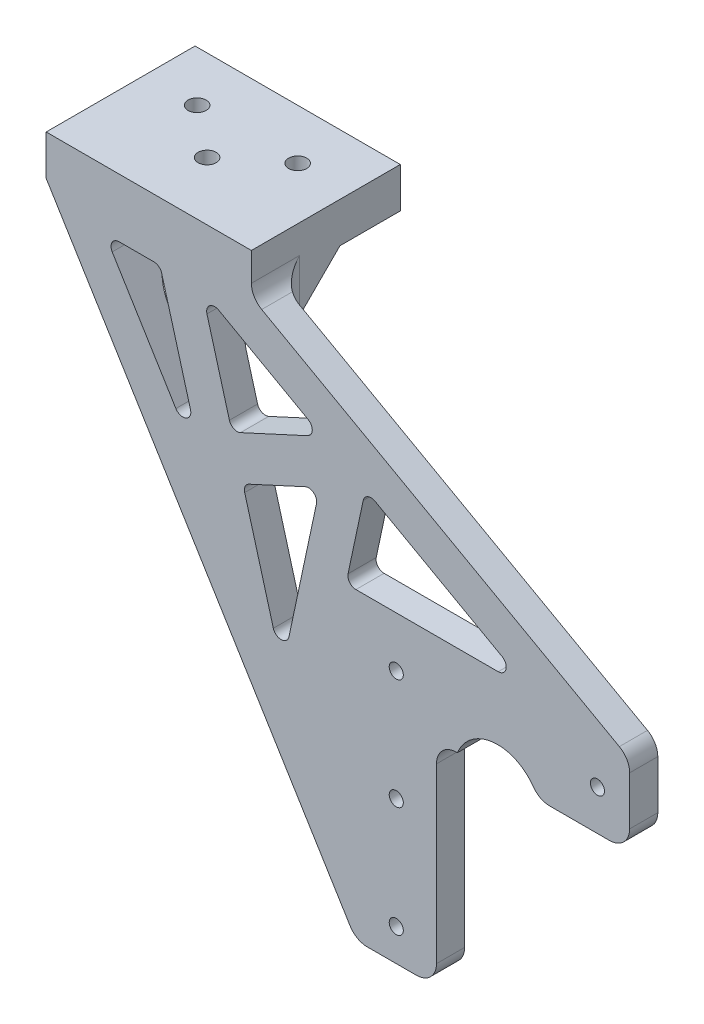
SolidWorks part; units mm, degrees
material "ABS"
ref_plane "Front Plane" through (0, 0, 0) normal (0, 0, 1) x (1, 0, 0)
ref_plane "Top Plane" through (0, 0, 0) normal (0, 1, 0) x (1, 0, 0)
ref_plane "Right Plane" through (0, 0, 0) normal (1, 0, 0) x (0, 0, -1)
sketch "Sketch1" plane through (0, 0, 0) normal (0, 0, 1) x (1, 0, 0)
  line L0 (0, 0) -> (0, -10)
  line L1 (0, -10) -> (75.5366, -133.1148)
  line L2 (79.7984, -135.5) -> (92, -135.5)
  line L3 (97, -130.5) -> (97, -87.5)
  line L4 (102, -82.5) -> (102.2, -82.5)
  line L5 (145, -77.5) -> (145, -65.4344)
  line L6 (142.4381, -61.0691) -> (53.5619, -11.4309)
  line L7 (51, -7.0656) -> (51, 0)
  line L8 (51, 0) -> (0, 0)
  line L9 (125.1422, -82.5) -> (140, -82.5)
  line L10 (87, -127.5) -> (87, -72.5) construction
  line L11 (87, -72.5) -> (137, -72.5) construction
  line L12 (18.108, -14.5675) -> (26.771, -14.5675)
  line L13 (42.8552, -16.905) -> (65.1017, -29.3299)
  line L14 (112.3332, -60) -> (76.9713, -60)
  line L17 (28.6981, -16.0322) -> (35.8649, -41.8328)
  line L18 (75.0153, -57.583) -> (78.7777, -39.9344)
  line L19 (60.3372, -78.4725) -> (67.1742, -46.4018)
  line L20 (64.7198, -57.915) -> (69.5626, -35.1987) construction
  line L21 (39.9529, -19.1864) -> (45.5344, -39.2798)
  line L22 (37.9264, -11.891) -> (49.3072, -52.8619) construction
  line L23 (50.4211, -50.5921) -> (64.3822, -44.1679)
  line L25 (48.2975, -40.5614) -> (64.9625, -32.8929)
  line L27 (49.3301, -52.9443) -> (56.4541, -78.5908)
  line L29 (32.2332, -43.414) -> (16.4033, -17.6134)
  line L30 (81.709, -38.6053) -> (113.3084, -56.2539)
  line L31 (74.5, -60) -> (79.3428, -37.2837) construction
  line L32 (28.2912, -14.5675) -> (39.672, -55.5383) construction
  arc A0 (102.2, -82.5) -> (121.042, -80.3615) centre (112.2, -86.5324) cw
  arc A1 (53.5619, -11.4309) -> (51, -7.0656) centre (56, -7.0656) cw
  arc A2 (145, -65.4344) -> (142.4381, -61.0691) centre (140, -65.4344) ccw
  arc A3 (121.042, -80.3615) -> (125.1422, -82.5) centre (125.1422, -77.5) ccw
  arc A4 (140, -82.5) -> (145, -77.5) centre (140, -77.5) ccw
  arc A5 (97, -87.5) -> (102, -82.5) centre (102, -87.5) cw
  arc A6 (92, -135.5) -> (97, -130.5) centre (92, -130.5) ccw
  arc A7 (75.5366, -133.1148) -> (79.7984, -135.5) centre (79.7984, -130.5) ccw
  arc A8 (113.3084, -56.2539) -> (112.3332, -60) centre (112.3332, -58) cw
  arc A9 (78.7777, -39.9344) -> (81.709, -38.6053) centre (80.7338, -40.3514) cw
  arc A10 (76.9713, -60) -> (75.0153, -57.583) centre (76.9713, -58) cw
  arc A11 (60.3372, -78.4725) -> (56.4541, -78.5908) centre (58.3812, -78.0555) cw
  arc A12 (49.3301, -52.9443) -> (50.4211, -50.5921) centre (51.2571, -52.409) cw
  arc A13 (67.1742, -46.4018) -> (64.3822, -44.1679) centre (65.2182, -45.9848) ccw
  arc A14 (64.9625, -32.8929) -> (65.1017, -29.3299) centre (64.1265, -31.0761) ccw
  arc A15 (39.9529, -19.1864) -> (42.8552, -16.905) centre (41.8799, -18.6511) cw
  arc A16 (48.2975, -40.5614) -> (45.5344, -39.2798) centre (47.4614, -38.7445) cw
  arc A17 (35.8649, -41.8328) -> (32.2332, -43.414) centre (33.9379, -42.368) cw
  arc A18 (28.6981, -16.0322) -> (26.771, -14.5675) centre (26.771, -16.5675) ccw
  arc A19 (18.108, -14.5675) -> (16.4033, -17.6134) centre (18.108, -16.5675) ccw
  point P14 (87, -100)
  point P18 (51, -10)
  point P21 (145, -62.5)
  point P24 (122.2, -82.5)
  point P27 (145, -82.5)
  point P30 (97, -82.5)
  point P33 (97, -135.5)
  point P36 (77, -135.5)
  dimension "D10" = 20
  dimension "D13" = 5
  dimension "D17" = 2
  dimension "D1" = 10
  dimension "D2" = 51
  dimension "D3" = 125.5
  dimension "D4" = 77
  dimension "D5" = 20
  dimension "D6" = 48
  dimension "D7" = 53
  dimension "D8" = 20
  dimension "D9" = 10
  dimension "D11" = 6.75
  dimension "D12" = 42.8
  dimension "D14" = 10
  dimension "D15" = 8
  dimension "D16" = 10
  dimension "D18" = 10
  dimension "D19" = 14.5675
  dimension "D21" = 12.5
  dimension "D22" = 8
  dimension "D23" = 10
  dimension "D24" = 10
extrude "Boss-Extrude1" add sketch "Sketch1" along normal blind 7
sketch "Sketch2" plane through (0, 0, 0) normal (0, 0, -1) x (-1, 0, 0)
  line L1 (-51, 0) -> (0, 0)
  line L2 (-51, 0) -> (-51, -10)
  line L3 (-51, -10) -> (0, -10)
  line L4 (0, 0) -> (0, -10)
extrude "Boss-Extrude2" add sketch "Sketch2" along normal blind 30
chamfer "Chamfer1" distance 15 angle 45 1 edges at (25.5, -10, 0)
fillet "Fillet1" radius 5 1 edges at (51, -14.2598, 0)
hole_wizard "Ø3.5 (3.5) Diameter Hole1" positions "Sketch3" profile "Sketch4" hole size "Ø3.5" standard "ANSI Metric" end condition through all
sketch "Sketch3" plane through (0, 0, 7) normal (0, 0, 1) x (1, 0, 0)
  point P0 (87, -127.5)
  point P3 (87, -100)
  point P6 (87, -72.5)
  point P9 (137, -72.5)
sketch "Sketch4" plane through (87, -127.5, 7) normal (1, 0, 0) x (0, -1, 0)
  line L0 (0, 0) -> (0, 37)
  line L1 (0, 37) -> (1.75, 37)
  line L2 (1.75, 37) -> (1.75, 0)
  line L5 (1.75, 0) -> (0, 0)
  line L11 (0, -6.35) -> (0, 107.95) construction
  dimension "Thru Hole Dia." = 3.5
  dimension "Thru Hole Depth" = 37
sketch "Sketch5" plane through (0, 0, 0) normal (0, 1, 0) x (1, 0, 0)
  line L0 (25.5, 30) -> (25.5, -7) construction
  line L1 (0, 30) -> (51, 30) construction
  line L2 (51, -7) -> (0, -7) construction
  line L3 (13, 17.5) -> (38, 17.5) construction
  point P6 (25.5, 7.5)
  dimension "D1" = 14.5
  dimension "D2" = 10
  dimension "D3" = 25
  dimension "D4" = 12.5
hole_wizard "Ø4.5 (4.5) Diameter Hole1" positions "Sketch6" profile "Sketch7" hole size "Ø4.5" standard "ANSI Metric" end condition through all
sketch "Sketch6" plane through (0, 0, 0) normal (0, 1, 0) x (1, 0, 0)
  point P0 (13, 17.5)
  point P3 (25.5, 7.5)
  point P6 (38, 17.5)
sketch "Sketch7" plane through (13, 0, -17.5) normal (1, 0, 0) x (0, 0, 1)
  line L0 (0, 0) -> (0, 135.5)
  line L1 (0, 135.5) -> (2.25, 135.5)
  line L2 (2.25, 135.5) -> (2.25, 0)
  line L5 (2.25, 0) -> (0, 0)
  line L11 (0, -6.35) -> (0, 107.95) construction
  dimension "Thru Hole Dia." = 4.5
  dimension "Thru Hole Depth" = 135.5
ref_plane "Plane1" through (0, -7, 0) normal (0, 1, 0) x (1, 0, 0)
sketch "Sketch8" plane through (0, -7, 0) normal (0, 1, 0) x (1, 0, 0)
  line L0 (13, 17.5) -> (16.4641, 17.5) construction
  line L1 (9.5359, 17.5) -> (11.2679, 14.5)
  line L2 (11.2679, 14.5) -> (14.7321, 14.5)
  line L3 (14.7321, 14.5) -> (16.4641, 17.5)
  line L4 (16.4641, 17.5) -> (14.7321, 20.5)
  line L5 (14.7321, 20.5) -> (11.2679, 20.5)
  line L6 (11.2679, 20.5) -> (9.5359, 17.5)
  line L7 (22.0359, 7.5) -> (23.7679, 4.5)
  line L8 (23.7679, 4.5) -> (27.2321, 4.5)
  line L9 (27.2321, 4.5) -> (28.9641, 7.5)
  line L10 (28.9641, 7.5) -> (27.2321, 10.5)
  line L11 (27.2321, 10.5) -> (23.7679, 10.5)
  line L12 (23.7679, 10.5) -> (22.0359, 7.5)
  line L13 (34.5359, 17.5) -> (36.2679, 14.5)
  line L14 (36.2679, 14.5) -> (39.7321, 14.5)
  line L15 (39.7321, 14.5) -> (41.4641, 17.5)
  line L16 (41.4641, 17.5) -> (39.7321, 20.5)
  line L17 (39.7321, 20.5) -> (36.2679, 20.5)
  line L18 (36.2679, 20.5) -> (34.5359, 17.5)
  line L19 (25.5, 7.5) -> (28.9641, 7.5) construction
  line L20 (38, 17.5) -> (41.4641, 17.5) construction
  circle A0 centre (13, 17.5) radius 3 construction
  circle A1 centre (25.5, 7.5) radius 3 construction
  circle A2 centre (38, 17.5) radius 3 construction
  dimension "D1" = 6
  dimension "D2" = 6
  dimension "D3" = 6
extrude "Cut-Extrude1" cut sketch "Sketch8" against normal through all
fillet "Fillet2" radius 10 2 edges at (15.0693, -25, 0) (36.3785, -25, 0)
